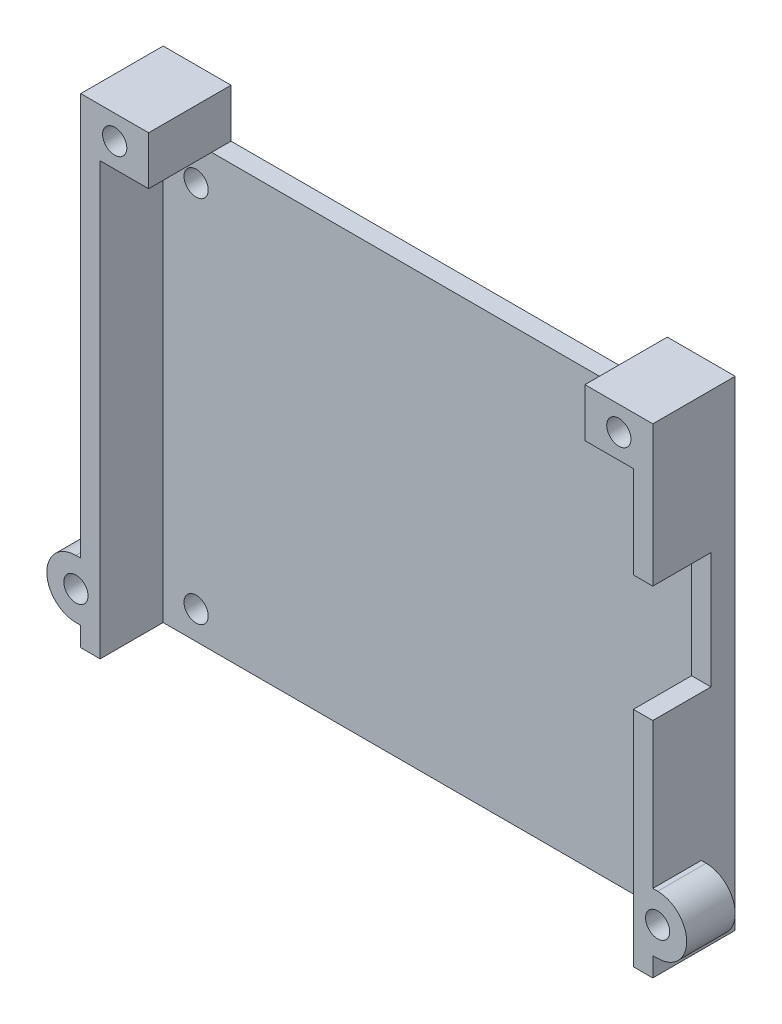
SolidWorks part; units mm, degrees
ref_plane "Front Plane" through (0, 0, 0) normal (0, 0, 1) x (1, 0, 0)
ref_plane "Top Plane" through (0, 0, 0) normal (0, 1, 0) x (1, 0, 0)
ref_plane "Right Plane" through (0, 0, 0) normal (1, 0, 0) x (0, 0, -1)
sketch "Sketch1" plane through (0, 0, 0) normal (0, 1, 0) x (1, 0, 0)
  line L0 (0, 0) -> (2, 0)
  line L1 (0, 0) -> (59, 0) construction
  line L2 (0, 0) -> (0, 8.5)
  line L3 (0, 8.5) -> (59, 8.5)
  line L4 (59, 0) -> (59, 8.5)
  line L5 (2, 0) -> (2, 6.5)
  line L6 (2, 6.5) -> (57, 6.5)
  line L7 (57, 6.5) -> (57, 0)
  line L8 (57, 0) -> (59, 0)
  dimension "D1" = 59
  dimension "D2" = 8.5
  dimension "D3" = 2
  dimension "D4" = 6.5
  dimension "D5" = 55
extrude "Boss-Extrude1" add sketch "Sketch1" along normal blind 44.5
sketch "Sketch2" plane through (59, 0, 0) normal (1, 0, 0) x (0, 0, -1)
  line L0 (0, 0) -> (0, 23) construction
  line L1 (0, 44.5) -> (0, 0) construction
  line L2 (0, 23) -> (6, 23)
  line L3 (6, 23) -> (6, 35)
  line L4 (6, 35) -> (0, 35)
  line L5 (0, 35) -> (0, 23)
  dimension "D1" = 23
  dimension "D2" = 6
  dimension "D3" = 12
extrude "Cut-Extrude1" cut sketch "Sketch2" against normal blind 10
sketch "Sketch3" plane through (0, 0, -8.5) normal (0, 0, -1) x (-1, 0, 0)
  line L0 (-59, 0) -> (-59, 8) construction
  line L1 (-59, 44.5) -> (-59, 0) construction
  line L2 (-59, 8) -> (-59, 2)
  line L3 (-59, 5) -> (-59.5, 5) construction
  line L4 (-59, 8) -> (-59.5, 8)
  line L5 (-59, 2) -> (-59.5, 2)
  line L6 (0, 0) -> (0, 8) construction
  line L7 (0, 44.5) -> (0, 0) construction
  line L8 (0, 8) -> (0.5, 8)
  line L9 (0, 8) -> (0, 2)
  line L10 (0, 2) -> (0.5, 2)
  line L11 (0, 5) -> (0.5, 5) construction
  arc A0 (-59.5, 8) -> (-59.5, 2) centre (-59.5, 5) ccw
  circle A1 centre (-59.5, 5) radius 1.25
  arc A2 (0.5, 8) -> (0.5, 2) centre (0.5, 5) cw
  circle A3 centre (0.5, 5) radius 1.25
  line M5 (0, 0) -> (0, 44.5)
  line M7 (-59, 44.5) -> (-59, 0)
  dimension "D4" = 3
  dimension "D5" = 2.5
  dimension "D11" = 3
  dimension "D12" = 2.5
  dimension "D1" = 8
  dimension "D2" = 6
  dimension "D3" = 0.5
  dimension "D6" = 8
  dimension "D7" = 0.5
  dimension "D8" = 6
  dimension "D9" = 0.5
extrude "Boss-Extrude2" add sketch "Sketch3" against normal blind 8.5 contours A1 L4 A0 L5 M7 | A3 L10 A2 L8 M5 region at (59.0695, 7.0728, -8.5) region at (-0.25, 7.9305, -8.5)
extrude "Cut-Extrude2" cut sketch "Sketch3<3>" against normal blind 11 contours L2 A1 | L9 A3 region at (58.6906, 5, -8.5) region at (0.3094, 5, -8.5)
sketch "Sketch3<3>" plane through (0, 0, -8.5) normal (0, 0, -1) x (-1, 0, 0) same geometry as "Sketch3"
sketch "Sketch4" plane through (0, 44.5, 0) normal (0, 1, 0) x (1, 0, 0)
  line L0 (59, 8.5) -> (0, 8.5) construction
  line L1 (0, 0) -> (7, 0)
  line L2 (0, 0) -> (0, 8.5)
  line L3 (0, 8.5) -> (7, 8.5)
  line L4 (7, 0) -> (7, 8.5)
  line L6 (59, 0) -> (52, 0)
  line L7 (59, 0) -> (59, 8.5)
  line L8 (59, 8.5) -> (52, 8.5)
  line L9 (52, 0) -> (52, 8.5)
  dimension "D1" = 7
  dimension "D2" = 7
extrude "Boss-Extrude3" add sketch "Sketch4" along normal blind 5
sketch "Sketch5" plane through (0, 0, -8.5) normal (0, 0, -1) x (-1, 0, 0)
  line L0 (-59, 49.5) -> (-52, 44.5) construction
  line L1 (0, 49.5) -> (-7, 44.5) construction
  circle A0 centre (-55.5, 47) radius 1.25
  circle A1 centre (-3.5, 47) radius 1.25
  dimension "D1" = 2.5
  dimension "D2" = 2.5
extrude "Cut-Extrude3" cut sketch "Sketch5" against normal through all
sketch "Sketch7" plane through (0, 0, -8.5) normal (0, 0, -1) x (-1, 0, 0)
  line L0 (-59, 0) -> (-59, 2.9) construction
  line L1 (-59, 2) -> (-59, 0) construction
  line L2 (-59, 2.9) -> (0, 2.9) construction
  line L3 (0, 2) -> (0, 0) construction
  line L4 (-53.6, 2.9) -> (-5.4, 2.9)
  line L5 (-53.6, 2.9) -> (-53.6, 40.95) construction
  line L6 (-53.6, 40.95) -> (-5.4, 40.95) construction
  circle A0 centre (-53.6, 2.9) radius 1.25
  circle A1 centre (-5.4, 2.9) radius 1.25
  circle A2 centre (-53.6, 40.95) radius 1.25
  circle A3 centre (-5.4, 40.95) radius 1.25
  point P11 (-29.5, 2.9)
  dimension "D3" = 2.5
  dimension "D4" = 2.5
  dimension "D6" = 2.5
  dimension "D8" = 2.5
  dimension "D1" = 2.9
  dimension "D2" = 48.2
  dimension "D5" = 38.05
  dimension "D7" = 48.2
extrude "Cut-Extrude4" cut sketch "Sketch7" against normal blind 10 contours A2 | A3 | A1 | A0 region at (5.4, 4.1146, -8.5) region at (54.8146, 2.9, -8.5) region at (53.6, 40.95, -8.5) region at (5.4, 40.95, -8.5)
extrude "Cut-Extrude6" cut sketch "Sketch3<4>" against normal blind 3.5 contours A1 L4 A0 L5 M7 | A3 L10 A2 L8 M5 region at (59.0695, 7.0728, -8.5) region at (-0.25, 7.9305, -8.5)
sketch "Sketch3<4>" plane through (0, 0, -8.5) normal (0, 0, -1) x (-1, 0, 0) same geometry as "Sketch3"
extrude "Boss-Extrude4" add sketch "Sketch3<5>" against normal blind 3 contours L9 A3 | L2 A1 region at (58.6906, 5, -8.5) region at (0.3094, 5, -8.5)
sketch "Sketch3<5>" plane through (0, 0, -8.5) normal (0, 0, -1) x (-1, 0, 0) same geometry as "Sketch3"
